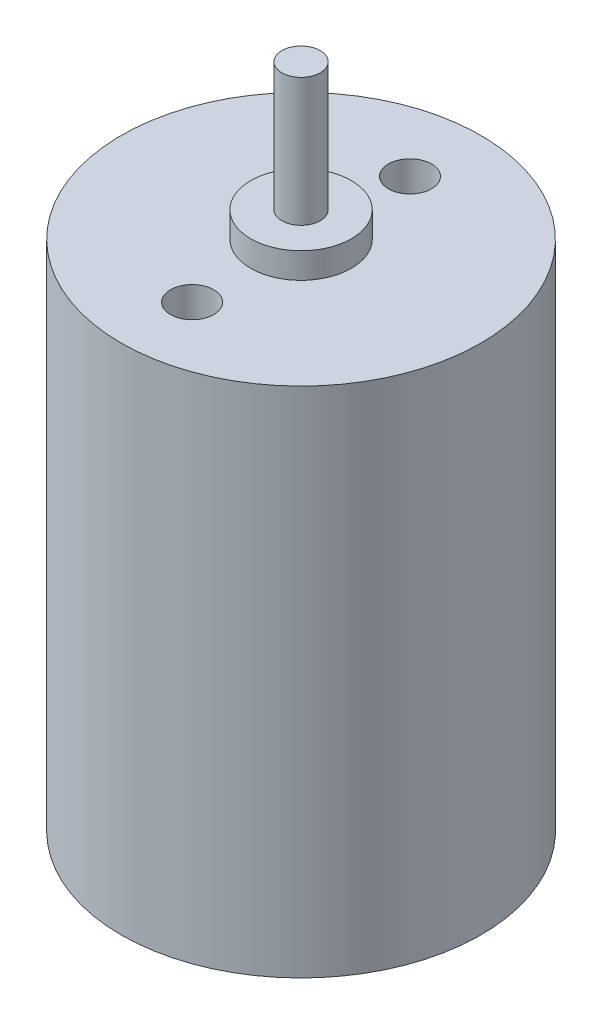
SolidWorks part; units mm, degrees
ref_plane "前视基准面" through (0, 0, 0) normal (0, 0, 1) x (1, 0, 0)
ref_plane "上视基准面" through (0, 0, 0) normal (0, 1, 0) x (1, 0, 0)
ref_plane "右视基准面" through (0, 0, 0) normal (1, 0, 0) x (0, 0, -1)
other "Configuration Table"
sketch "草圖2" plane through (0, 0, 0) normal (0, 1, 0) x (1, 0, 0)
  line L0 (0, -23.5253) -> (0, 23.5253)
  circle A1 centre (0, 0) radius 14.0363
  circle A3 centre (0, 0) radius 3.9302
  circle A4 centre (0, 8.5) radius 1.6844
  circle A5 centre (0, -8.5) radius 1.6844
  circle A6 centre (0, 0) radius 1.5
  point P7 (0, 0)
  dimension "D1" = 8.5
  dimension "D2" = 2
extrude "填料-伸長1" add sketch "草圖2" against normal blind 40 contours A1
extrude "填料-伸長2" add sketch "草圖2<4>" along normal blind 2 contours A3
sketch "草圖2<4>" plane through (0, 0, 0) normal (0, 1, 0) x (1, 0, 0) same geometry as "草圖2"
extrude "填料-伸長3" add sketch "草圖2<5>" along normal blind 12 contours A6
sketch "草圖2<5>" plane through (0, 0, 0) normal (0, 1, 0) x (1, 0, 0) same geometry as "草圖2"
extrude "除料-伸長1" cut sketch "草圖2<6>" against normal blind 6 contours A4 | A5
sketch "草圖2<6>" plane through (0, 0, 0) normal (0, 1, 0) x (1, 0, 0) same geometry as "草圖2"
